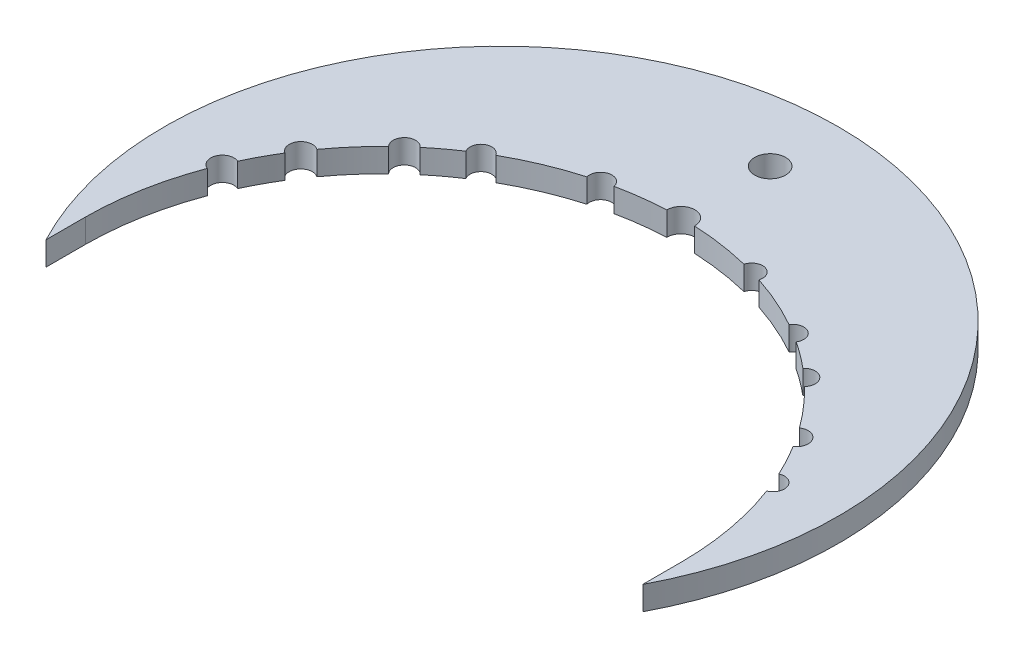
SolidWorks part; units mm, degrees
ref_plane "Front Plane" through (0, 0, 0) normal (0, 0, 1) x (1, 0, 0)
ref_plane "Top Plane" through (0, 0, 0) normal (0, 1, 0) x (1, 0, 0)
ref_plane "Right Plane" through (0, 0, 0) normal (1, 0, 0) x (0, 0, -1)
sketch "Sketch1" plane through (0, 0, 0) normal (0, 1, 0) x (1, 0, 0)
  line L0 (-28.5429, 0) -> (-28.5429, -8.3131)
  line L1 (97.1344, 0) -> (97.1344, -8.3131)
  arc A0 (-28.5429, 0) -> (97.1344, 0) centre (34.2958, -0.278) cw
  arc A1 (97.1344, -8.3131) -> (-28.5429, -8.3131) centre (34.2958, 24.7334) ccw
  circle A2 centre (34.2958, 81.3377) radius 3.25
  arc A3 (-22.6891, 26.2078) -> (-24.2821, 21.5933) centre (-23.678, 23.9669) ccw
  arc A4 (-16.5097, 36.7029) -> (-19.2195, 32.6597) centre (-17.9037, 34.7075) ccw
  arc A5 (-6.0029, 47.9381) -> (-9.498, 44.7873) centre (-7.7799, 46.3954) ccw
  arc A6 (3.4125, 54.4486) -> (-0.4767, 52.0637) centre (1.4462, 53.2914) ccw
  arc A7 (37.2172, 62.4933) -> (31.3744, 62.4933) centre (34.2958, 62.5613) ccw
  arc A8 (69.0682, 52.0637) -> (65.1791, 54.4486) centre (67.1453, 53.2914) ccw
  arc A9 (78.0895, 44.7873) -> (74.5944, 47.9381) centre (76.3714, 46.3954) ccw
  arc A10 (87.811, 32.6597) -> (85.1012, 36.7029) centre (86.4953, 34.7075) ccw
  arc A11 (93.1475, 21.7503) -> (91.3081, 26.1487) centre (92.2695, 23.9669) ccw
  arc A12 (53.8364, 59.4459) -> (49.4123, 60.716) centre (51.6359, 60.1214) ccw
  arc A13 (21.5262, 61.2501) -> (16.9348, 60.1155) centre (19.2198, 60.726) ccw
  point P41 (34.2958, 81.3377)
  dimension "D1" = 6.5
extrude "Boss-Extrude1" add sketch "Sketch1" along normal blind 5 contours A13 A0 A7 A12 A8 A9 A10 A11 L1 A1 L0 A4 A5 A6 A2 region at (-30.3032, 0, 4.1565)
